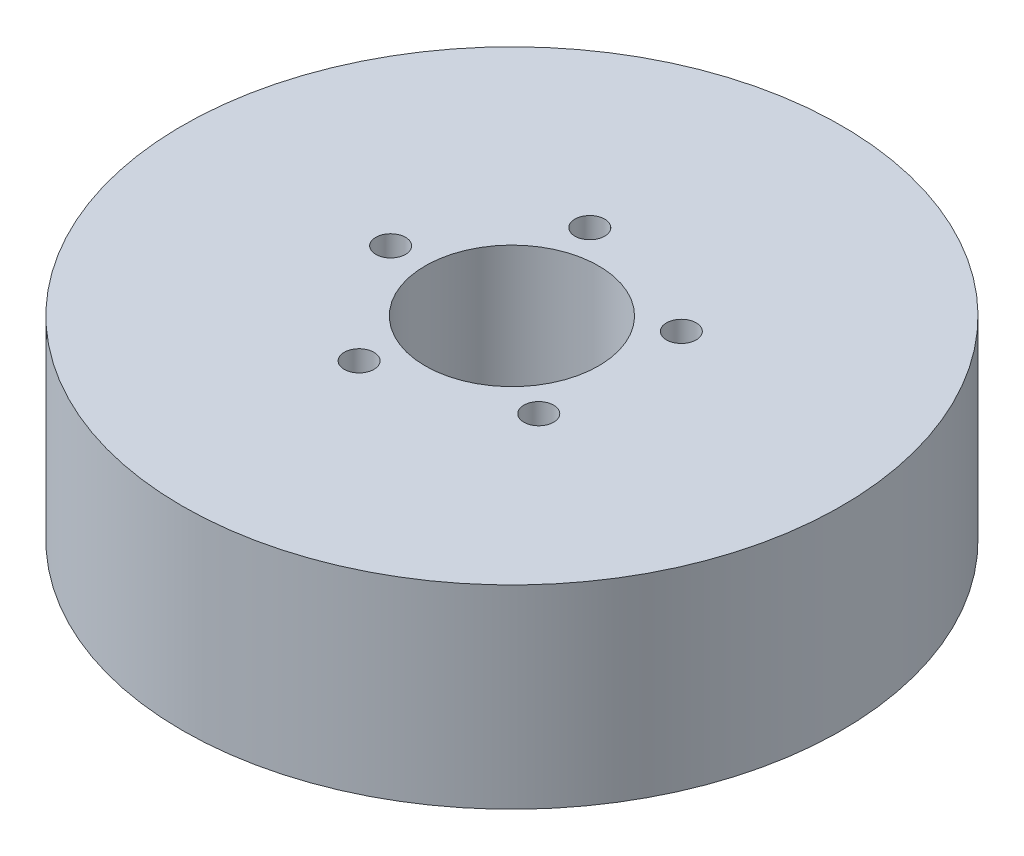
SolidWorks part; units mm, degrees
ref_plane "Front Plane" through (0, 0, 0) normal (0, 0, 1) x (1, 0, 0)
ref_plane "Top Plane" through (0, 0, 0) normal (0, 1, 0) x (1, 0, 0)
ref_plane "Right Plane" through (0, 0, 0) normal (1, 0, 0) x (0, 0, -1)
sketch "Sketch1" plane through (0, 0, 0) normal (0, 1, 0) x (1, 0, 0)
  circle A0 centre (0, 0) radius 47.5
  dimension "FLANGE_OD" = 95
extrude "Boss-Extrude1" add sketch "Sketch1" along normal blind 28
sketch "Sketch2" plane through (0, 0, 0) normal (0, 1, 0) x (1, 0, 0)
  circle A0 centre (0, 0) radius 12.5
  dimension "BORE_D" = 25
extrude "Cut-Extrude1" cut sketch "Sketch2" along normal through all
sketch "Sketch3" plane through (0, 28, 0) normal (0, 1, 0) x (1, 0, 0)
  circle A0 centre (0, 0) radius 17.4811 construction
  circle A1 centre (-17.4811, 0) radius 2.141
  dimension "BOLT_D" = 4.2819
  dimension "BOLT_PCD" = 34.9622
extrude "Cut-Extrude2" cut sketch "Sketch3" against normal blind 19.4681
pattern_circular "CirPattern1" count 5 over 360 about axis through (0, 0, 0) along (0, 1, 0) of "Cut-Extrude2"
